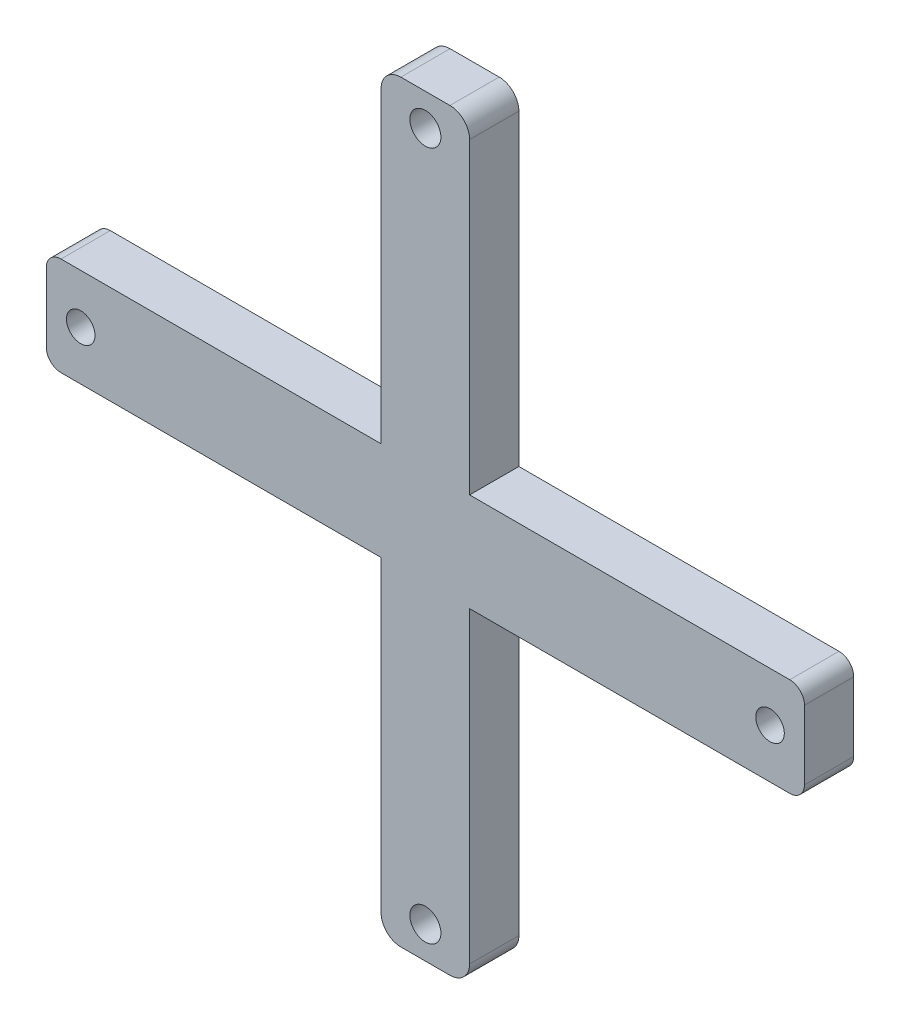
SolidWorks part; units mm, degrees
ref_plane "Front Plane" through (0, 0, 0) normal (0, 0, 1) x (1, 0, 0)
ref_plane "Top Plane" through (0, 0, 0) normal (0, 1, 0) x (1, 0, 0)
ref_plane "Right Plane" through (0, 0, 0) normal (1, 0, 0) x (0, 0, -1)
sketch "Sketch1" plane through (0, 0, 0) normal (0, 0, 1) x (1, 0, 0)
  line L1 (93.98, -12.7) -> (-93.98, -12.7)
  line L2 (97.79, -8.89) -> (97.79, 8.89)
  line L3 (93.98, 12.7) -> (-93.98, 12.7)
  line L4 (-97.79, -8.89) -> (-97.79, 8.89)
  line L5 (97.79, -12.7) -> (-97.79, 12.7) construction
  line L6 (97.79, 12.7) -> (-97.79, -12.7) construction
  arc A0 (97.79, 8.89) -> (93.98, 12.7) centre (93.98, 8.89) ccw
  arc A1 (93.98, -12.7) -> (97.79, -8.89) centre (93.98, -8.89) ccw
  arc A2 (-93.98, -12.7) -> (-97.79, -8.89) centre (-93.98, -8.89) cw
  arc A3 (-93.98, 12.7) -> (-97.79, 8.89) centre (-93.98, 8.89) ccw
  circle A4 centre (-88.9, 0) radius 3.683
  circle A5 centre (88.9, 0) radius 3.683
  point P0 (0, 0)
  dimension "D3" = 3.81
  dimension "D6" = 7.366
  dimension "D7" = 7.366
  dimension "D1" = 25.4
  dimension "D2" = 195.58
  dimension "D4" = 88.9
  dimension "D5" = 88.9
extrude "Boss-Extrude1" add sketch "Sketch1" along normal blind 12.7
sketch "Sketch3" plane through (0, 0, 12.7) normal (0, 0, 1) x (1, 0, 0)
  line L1 (-6.3354, -97.155) -> (6.3354, -97.155)
  line L2 (-11.4154, -92.075) -> (-11.4154, 92.075)
  line L3 (-6.3354, 97.155) -> (6.3354, 97.155)
  line L4 (11.4154, -92.075) -> (11.4154, 92.075)
  line L5 (-11.4154, -97.155) -> (11.4154, 97.155) construction
  line L6 (-11.4154, 97.155) -> (11.4154, -97.155) construction
  arc A0 (-6.3354, -97.155) -> (-11.4154, -92.075) centre (-6.3354, -92.075) cw
  arc A1 (6.3354, -97.155) -> (11.4154, -92.075) centre (6.3354, -92.075) ccw
  arc A2 (-11.4154, 92.075) -> (-6.3354, 97.155) centre (-6.3354, 92.075) cw
  arc A3 (6.3354, 97.155) -> (11.4154, 92.075) centre (6.3354, 92.075) cw
  circle A4 centre (0, 88.9) radius 4
  circle A5 centre (0, -88.9) radius 4
  point P0 (0, 0)
  dimension "D1" = 5.08
  dimension "D3" = 88.9
  dimension "D5" = 8
  dimension "D6" = 8
  dimension "D2" = 88.9
  dimension "D4" = 184.15
extrude "Boss-Extrude3" add sketch "Sketch3" against normal through all
sketch "Sketch2" plane through (0, 0, 0) normal (0, 0, -1) x (-1, 0, 0)
  circle A0 centre (-88.9, 0) radius 3.683
  circle A1 centre (88.9, 0) radius 3.683
  circle A2 centre (0, 88.9) radius 4
  circle A3 centre (0, -88.9) radius 4
extrude "Boss-Extrude2" add sketch "Sketch2" against normal blind 6.35
